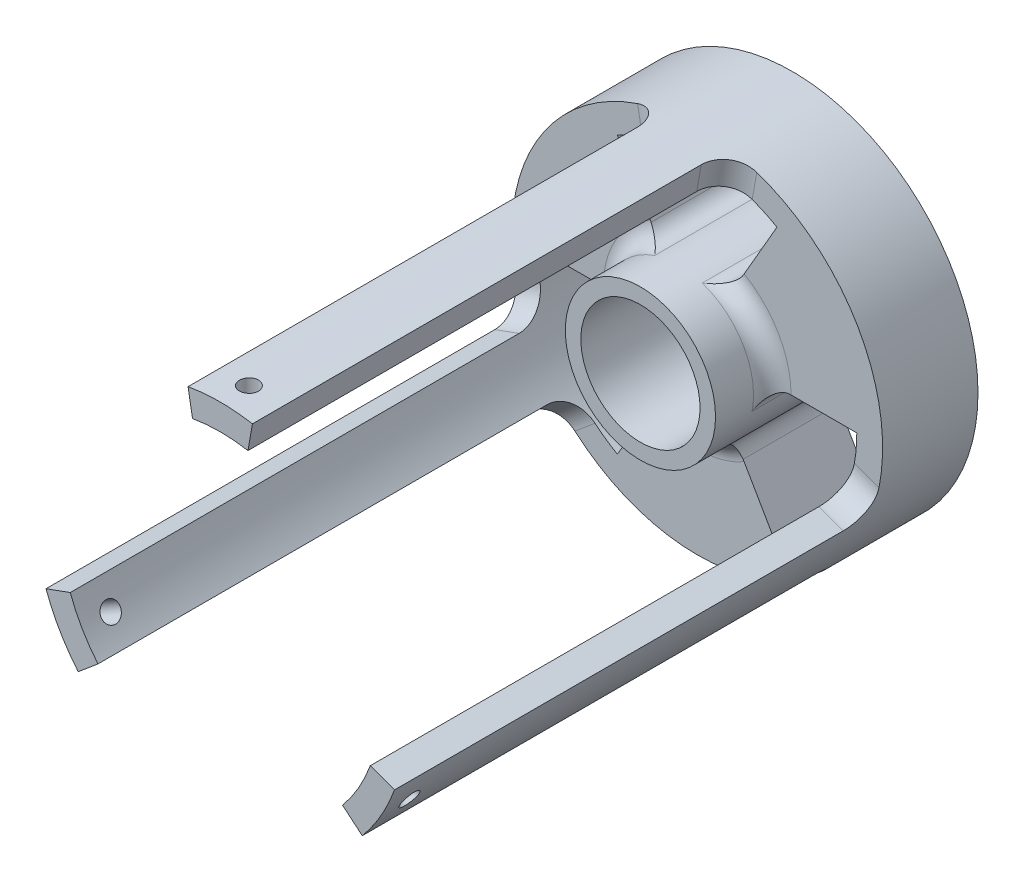
SolidWorks part; units mm, degrees
ref_plane "Front" through (0, 0, 0) normal (0, 0, 1) x (1, 0, 0)
ref_plane "Top" through (0, 0, 0) normal (0, 1, 0) x (1, 0, 0)
ref_plane "Right" through (0, 0, 0) normal (1, 0, 0) x (0, 0, -1)
sketch "Sketch1" plane through (0, 0, 0) normal (0, 0, 1) x (1, 0, 0)
  circle A0 centre (0, 0) radius 9.875
  dimension "D1" = 19.75
extrude "Boss-Extrude1" add sketch "Sketch1" along normal blind 5.08 contours A0
sketch "Sketch2" plane through (0, 0, 5.08) normal (0, 0, 1) x (1, 0, 0)
  circle A0 centre (0, 0) radius 3.175
  dimension "D1" = 6.35
extrude "Cut-Extrude1" cut sketch "Sketch2" against normal up to surface (5.08 mm away) up to face at (9.875, 0, 0)
sketch "Sketch3" plane through (0, 0, 5.08) normal (0, 0, 1) x (1, 0, 0)
  line L0 (-2, 3.4641) -> (-4.25, 7.3612)
  line L1 (2, 3.4641) -> (4.25, 7.3612)
  line L2 (-4, 0) -> (-8.5, 0)
  line L3 (-2, -3.4641) -> (-4.25, -7.3612)
  line L4 (2, -3.4641) -> (4.25, -7.3612)
  line L5 (4, 0) -> (8.5, 0)
  circle A0 centre (0, 0) radius 1.651
  circle A2 centre (0, 0) radius 4
  circle A3 centre (0, 0) radius 8.5
  dimension "D1" = 3.302
  dimension "D2" = 8
  dimension "D3" = 17
  dimension "D4" = 60
  dimension "D5" = 60
  dimension "D6" = 60
  dimension "D7" = 60
extrude "Cut-Extrude2" cut sketch "Sketch3" against normal up to next contours L2 A3 L3 A2 | L1 A3 L0 A2 | L4 A3 L5 A2 region at (0, 6.2261, 5.08) region at (-5.392, -3.1131, 5.08) region at (5.392, -3.1131, 5.08)
sketch "Sketch4" plane through (0, 0, 5.08) normal (0, 0, 1) x (1, 0, 0)
  line L0 (0, 11.3561) -> (0, 1.0944) construction
  line L1 (0, 0) -> (13.9354, -8.0456) construction
  line L2 (0, 0) -> (-11.2468, -6.4934) construction
  line L3 (2, 3.4641) -> (4.25, 7.3612) construction
  line L4 (-2, -3.4641) -> (-4.25, -7.3612) construction
  line L5 (2, -3.4641) -> (4.25, -7.3612) construction
  line L6 (1.7148, 9.725) -> (1.476, 8.3709)
  line L7 (-1.7148, 9.725) -> (-1.476, 8.3709)
  line L8 (-9.2795, -3.3774) -> (-7.9874, -2.9072)
  line L9 (-7.5647, -6.3475) -> (-6.5114, -5.4637)
  line L10 (7.5647, -6.3475) -> (6.5114, -5.4637)
  line L11 (9.2795, -3.3774) -> (7.9874, -2.9072)
  arc A0 (-9.2795, -3.3774) -> (-7.5647, -6.3475) centre (0, 0) ccw
  arc A1 (-7.9874, -2.9072) -> (-6.5114, -5.4637) centre (0, 0) ccw
  arc A2 (1.7148, 9.725) -> (-1.7148, 9.725) centre (0, 0) ccw
  arc A3 (1.476, 8.3709) -> (-1.476, 8.3709) centre (0, 0) ccw
  arc A4 (7.5647, -6.3475) -> (9.2795, -3.3774) centre (0, 0) ccw
  arc A5 (6.5114, -5.4637) -> (7.9874, -2.9072) centre (0, 0) ccw
  dimension "D1" = 17
  dimension "D2" = 19.75
  dimension "D3" = 20
  dimension "D4" = 20
  dimension "D5" = 30
  dimension "D6" = 30
  dimension "D7" = 30
  dimension "D8" = 20
extrude "Boss-Extrude2" add sketch "Sketch4" along normal blind 25.4
sketch "Sketch5" plane through (0, 0, 5.08) normal (0, 0, 1) x (1, 0, 0)
  line L0 (4, 0) -> (-3.175, 0)
  line L1 (-2, 3.4641) -> (-1.5875, 2.7496)
  arc A0 (-2, 3.4641) -> (4, 0) centre (0, 0) ccw construction
  arc A1 (-2, 3.4641) -> (4, 0) centre (0, 0) ccw
  circle A2 centre (0, 0) radius 3.175 construction
  arc A3 (-1.5875, 2.7496) -> (-3.175, 0) centre (0, 0) ccw
extrude "Boss-Extrude3" [suppressed] add sketch "Sketch5" along normal blind 3.0226 contours L1 A3 L0 A1
ref_plane "Plane1" through (0, 0, 28.956) normal (0, 0, 1) x (1, 0, 0)
sketch "Sketch7" plane through (0, 0, 28.956) normal (0, 0, 1) x (1, 0, 0)
  line L0 (0, 0) -> (0, 10.6675) construction
  line L1 (-0.508, 9.8619) -> (-0.508, 8.4848)
  line L3 (0, 9.875) -> (0, 8.5)
  arc A0 (-6.5114, -5.4637) -> (-4.25, -7.3612) centre (0, 0) ccw construction
  arc A1 (7.9874, -2.9072) -> (8.5, 0) centre (0, 0) ccw construction
  arc A2 (-1.476, 8.3709) -> (-4.25, 7.3612) centre (0, 0) ccw construction
  circle A3 centre (0, 0) radius 9.875 construction
  arc A4 (-6.5114, -5.4637) -> (-4.25, -7.3612) centre (0, 0) ccw
  arc A5 (7.9874, -2.9072) -> (8.5, 0) centre (0, 0) ccw
  arc A6 (-1.476, 8.3709) -> (-4.25, 7.3612) centre (0, 0) ccw
  circle A7 centre (0, 0) radius 9.875
  dimension "D1" = 0.508
ref_plane "Plane2" through (0, 9.875, 0) normal (0, 1, 0) x (1, 0, 0)
sketch "Sketch8" plane through (0, 9.875, 0) normal (0, 1, 0) x (1, 0, 0)
  circle A0 centre (0, -28.956) radius 0.508
  point P0 (0, -28.956)
  dimension "D1" = 1.016
extrude "Cut-Extrude3" cut sketch "Sketch8" against normal up to next
pattern_circular "CirPattern1" count 3 over 360 about axis through (0, 0, 30.48) along (0, 0, 1) of "Cut-Extrude3"
sketch "Sketch9" plane through (0, 0, 5.08) normal (0, 0, 1) x (1, 0, 0)
  circle A1 centre (0, 0) radius 4
  circle A2 centre (0, 0) radius 3.175 construction
  circle A3 centre (0, 0) radius 3.175
extrude "Boss-Extrude4" add sketch "Sketch9" along normal blind 3.0226
fillet "Fillet1" radius 1.5 6 edges at (8.6334, -3.1423, 5.08) (7.038, -5.9056, 5.08) (-7.038, -5.9056, 5.08) (-8.6334, -3.1423, 5.08) (-1.5954, 9.0479, 5.08) (1.5954, 9.0479, 5.08)
fillet "Fillet2" radius 1 3 edges at (0, -4, 5.08) (-3.4641, 2, 5.08) (3.4641, 2, 5.08)
fillet "Fillet3" radius 1 6 edges at (-4, 0, 3.04) (-2, -3.4641, 3.04) (-2, 3.4641, 3.04) (2, 3.4641, 3.04) (4, 0, 3.04) (2, -3.4641, 3.04)
